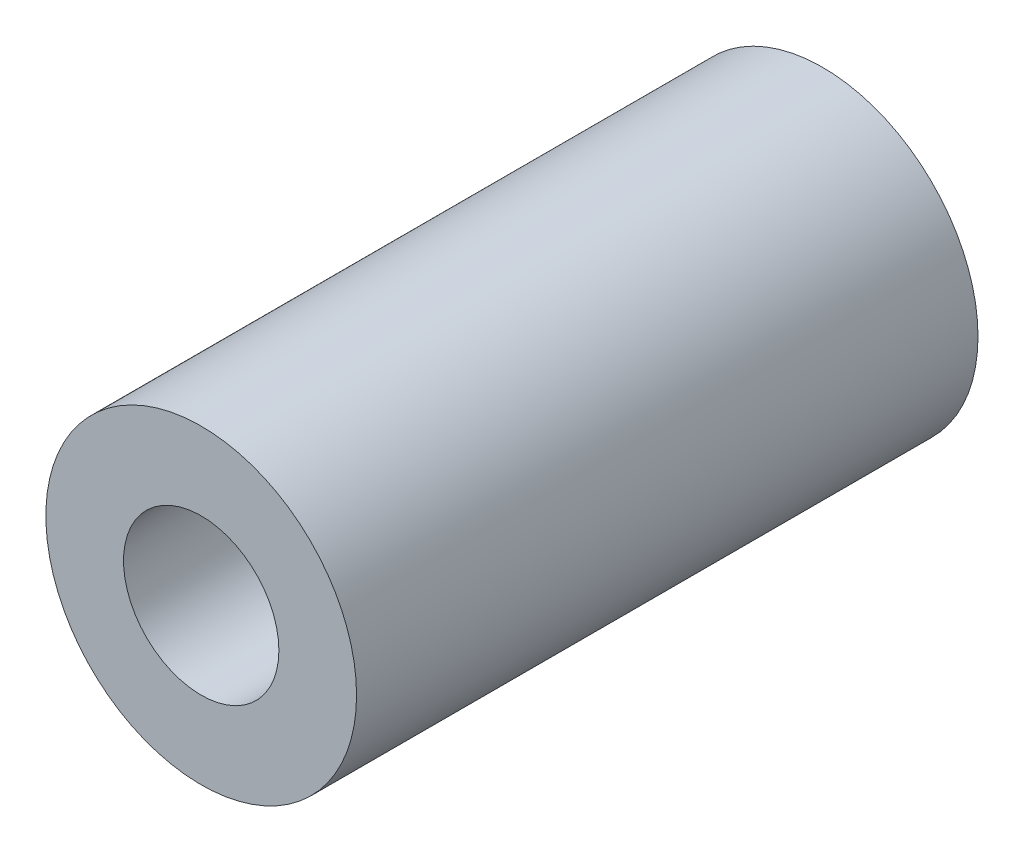
SolidWorks part; units mm, degrees
material "Nylon 101"
ref_plane "Front Plane" through (0, 0, 0) normal (0, 0, 1) x (1, 0, 0)
ref_plane "Top Plane" through (0, 0, 0) normal (0, 1, 0) x (1, 0, 0)
ref_plane "Right Plane" through (0, 0, 0) normal (1, 0, 0) x (0, 0, -1)
sketch "Sketch1" plane through (0, 0, 0) normal (0, 0, 1) x (1, 0, 0)
  circle A0 centre (0, 0) radius 6.35
  dimension "D1" = 12.7
extrude "Boss-Extrude1" add sketch "Sketch1" along normal blind 12.7 and the other way blind 12.7
sketch "Sketch2" plane through (0, 0, 12.7) normal (0, 0, 1) x (1, 0, 0)
  circle A0 centre (0, 0) radius 3.175
  dimension "D1" = 6.35
extrude "Cut-Extrude1" cut sketch "Sketch2" against normal through all
